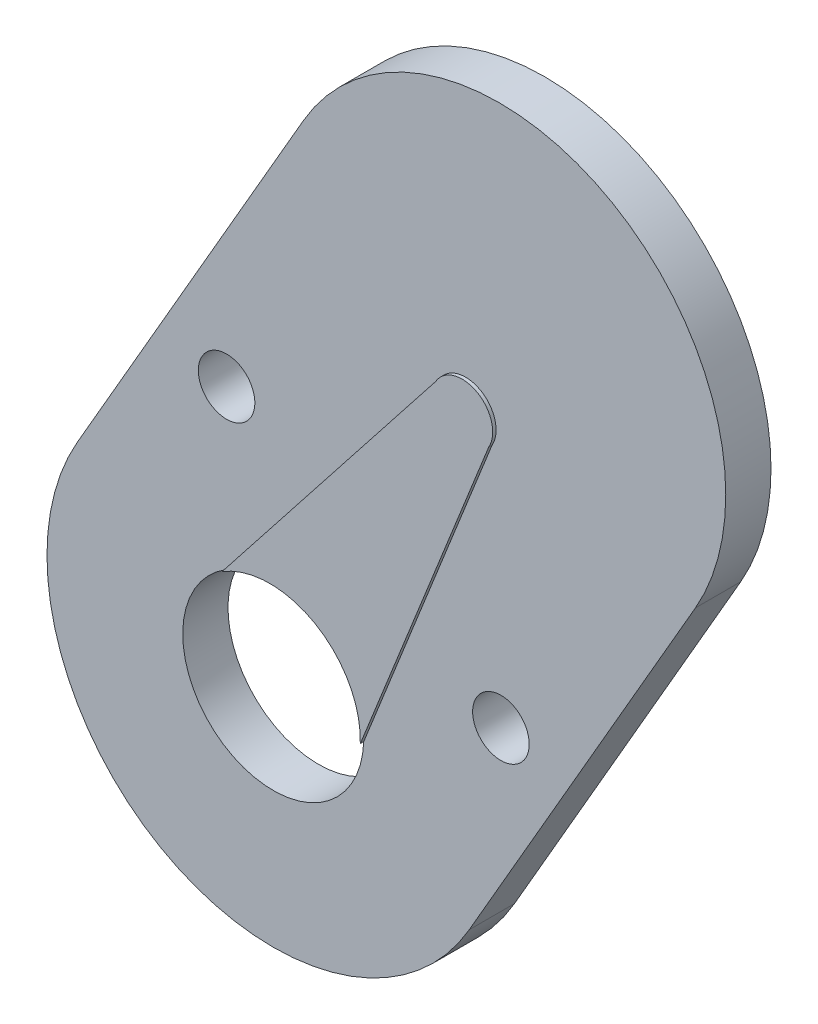
SolidWorks part; units mm, degrees
ref_plane "前视基准面" through (0, 0, 0) normal (0, 0, 1) x (1, 0, 0)
ref_plane "上视基准面" through (0, 0, 0) normal (0, 1, 0) x (1, 0, 0)
ref_plane "右视基准面" through (0, 0, 0) normal (1, 0, 0) x (0, 0, -1)
other "Configuration Table"
sketch "草图1" plane through (0, 0, 0) normal (0, 0, 1) x (1, 0, 0)
  line L0 (8.6603, -5) -> (18.6603, 12.3205)
  line L1 (18.6603, 12.3205) -> (1.3397, 22.3205)
  line L2 (1.3397, 22.3205) -> (-8.6603, 5)
  line L3 (-8.6603, 5) -> (8.6603, -5)
extrude "Retainer_plate_2mm" add sketch "草图1" along normal blind 2 from offset 2 offset against normal yes
sketch "草图2" plane through (0, 0, 0) normal (0, 0, 1) x (1, 0, 0)
  circle A0 centre (0, 0) radius 10
extrude "Retainer_plate_2mm_root" add sketch "草图2" along normal blind 2 from offset 2 offset against normal yes
sketch "草图3" plane through (0, 0, 0) normal (0, 0, 1) x (1, 0, 0)
  circle A0 centre (10, 17.3205) radius 10
extrude "Retainer_plate_2mm_tip" add sketch "草图3" along normal blind 2 from offset 2 offset against normal yes
sketch "草图4" plane through (0, 0, 0) normal (0, 0, 1) x (1, 0, 0)
  line L0 (3.2909, -1.9) -> (9.6691, 14.0474)
  line L1 (9.6691, 14.0474) -> (7.3309, 15.3974)
  line L2 (7.3309, 15.3974) -> (-3.2909, 1.9)
  line L3 (-3.2909, 1.9) -> (3.2909, -1.9)
extrude "Horn_contact_pad_0p15" add sketch "草图4" along normal blind 0.15 from offset 0
sketch "草图5" plane through (0, 0, 0) normal (0, 0, 1) x (1, 0, 0)
  circle A0 centre (0, 0) radius 3.8
extrude "Horn_contact_pad_0p15_root" add sketch "草图5" along normal blind 0.15 from offset 0
sketch "草图6" plane through (0, 0, 0) normal (0, 0, 1) x (1, 0, 0)
  circle A0 centre (8.5, 14.7224) radius 1.35
extrude "Horn_contact_pad_0p15_tip" add sketch "草图6" along normal blind 0.15 from offset 0
sketch "草图7" plane through (0, 0, 0) normal (0, 0, 1) x (1, 0, 0)
  circle A0 centre (0, 0) radius 4
extrude "Boss_clearance_8" cut sketch "草图7" along normal blind 2.5 from offset 2.1 offset against normal yes
sketch "草图8" plane through (0, 0, 0) normal (0, 0, 1) x (1, 0, 0)
  circle A0 centre (10.0622, 3.4282) radius 1.25
  circle A1 centre (-2.0622, 10.4282) radius 1.25
extrude "M2_clearance_2p5_pitch14" cut sketch "草图8" along normal blind 2.5 from offset 2.1 offset against normal yes
